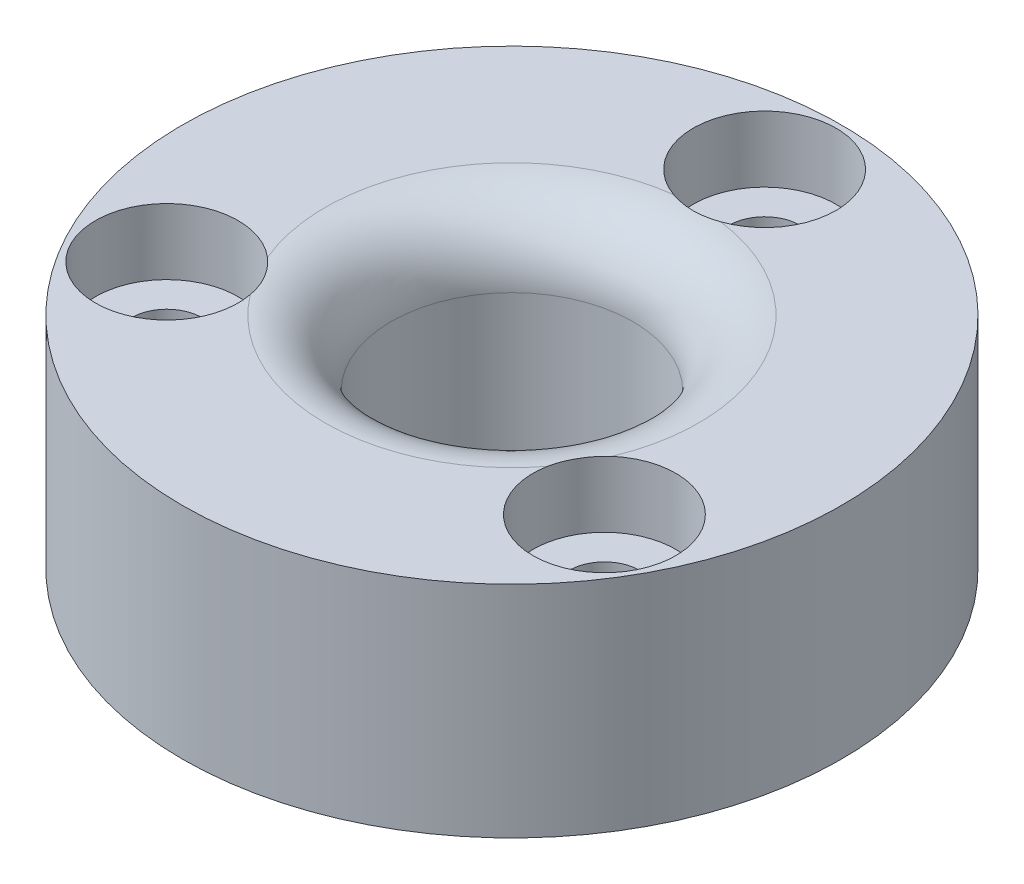
SolidWorks part; units mm, degrees
material "Alloy Steel (SS)"
ref_plane "Front Plane" through (0, 0, 0) normal (0, 0, 1) x (1, 0, 0)
ref_plane "Top Plane" through (0, 0, 0) normal (0, 1, 0) x (1, 0, 0)
ref_plane "Right Plane" through (0, 0, 0) normal (1, 0, 0) x (0, 0, -1)
sketch "Sketch1" plane through (0, 0, 0) normal (0, 1, 0) x (1, 0, 0)
  circle A0 centre (0, 0) radius 15
  circle A1 centre (0, 0) radius 5.5
  dimension "D1" = 30
  dimension "D2" = 11
extrude "Boss-Extrude1" add sketch "Sketch1" along normal blind 10
fillet "Fillet1" radius 3 1 edges at (0, 10, 5.5)
hole_wizard "CBORE for M3 SHCS1" positions "Sketch3" profile "Sketch2" counterbore size "M3" standard "Ansi Metric" end condition through all
sketch "Sketch3" plane through (0, 10, 0) normal (0, 1, 0) x (-1, 0, 0)
  line L0 (0, 0) -> (0, -15) construction
  circle A0 centre (0, 0) radius 15 construction
  point P0 (0, -11.5)
  dimension "D1" = 11.5
sketch "Sketch2" plane through (0, 10, -11.5) normal (1, 0, 0) x (0, 0, 1)
  line L0 (0, 0) -> (0, 10)
  line L1 (0, 10) -> (1.6, 10)
  line L3 (1.6, 10) -> (1.6, 3)
  line L4 (1.6, 3) -> (3.25, 3)
  line L5 (3.25, 3) -> (3.25, 0)
  line L7 (3.25, 0) -> (0, 0)
  line L11 (0, -6.35) -> (0, 107.95) construction
  dimension "Thru Hole Dia." = 3.2
  dimension "Thru Hole Depth" = 10
  dimension "C'Bore Dia." = 6.5
  dimension "C'Bore Depth" = 3
ref_axis "Axis1" through (0, 8, 0) along (0, -1, 0)
pattern_circular "CirPattern1" count 3 over 360 about axis through (0, 8, 0) along (0, -1, 0) of "CBORE for M3 SHCS1"
